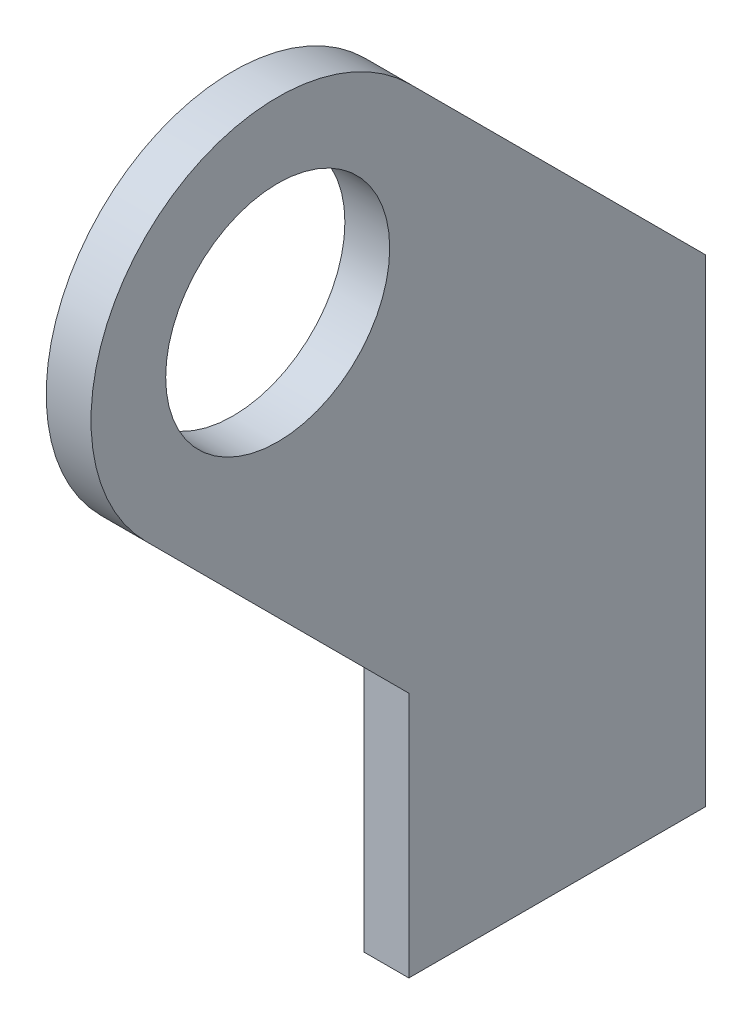
SolidWorks part; units mm, degrees
material "6061-T6 (SS)"
ref_plane "Front Plane" through (0, 0, 0) normal (0, 0, 1) x (1, 0, 0)
ref_plane "Top Plane" through (0, 0, 0) normal (0, 1, 0) x (1, 0, 0)
ref_plane "Right Plane" through (0, 0, 0) normal (1, 0, 0) x (0, 0, -1)
ref_axis "X" through (-88.99, 0, 0) along (1, 0, 0)
ref_axis "Y" through (0, 55, 0) along (0, -1, 0)
ref_axis "Z" through (0, 0, -88.99) along (0, 0, 1)
sketch "Sketch1" plane through (0, 0, 0) normal (1, 0, 0) x (0, 0, -1)
  line L0 (8.8388, 8.8388) -> (28.6522, -10.9745)
  line L1 (28.6522, -10.9745) -> (28.6522, -42.9745)
  line L2 (28.6522, -42.9745) -> (8.7823, -42.9745)
  line L3 (8.7823, -42.9745) -> (8.7823, -26.46)
  line L4 (8.7823, -26.46) -> (-8.8388, -8.8388)
  line L5 (8.7823, -10.9745) -> (8.7823, -42.9745) construction
  line L7 (8.7823, -42.9745) -> (68.7823, -42.9745) construction
  line L8 (8.7823, -10.9745) -> (68.7823, -10.9745) construction
  line L11 (8.8388, 8.8388) -> (25.6777, -8) construction
  circle A0 centre (0, 0) radius 7.5
  circle A1 centre (0, 0) radius 12.5
  point P6 (9.7454, -24.6297)
  point P11 (37.9004, -42.1434)
  point P16 (27.6344, -10.9745)
  point P17 (27.2296, -10.9745)
  dimension "D1" = 15
  dimension "D2" = 5
extrude "Boss-Extrude1" add sketch "Sketch1" along normal blind 3 contours A1 L4 L3 L2 L1 L0 | A1 A0 region at (0, -22.0795, -16.6142) region at (0, 4.6482, -11.2219)
